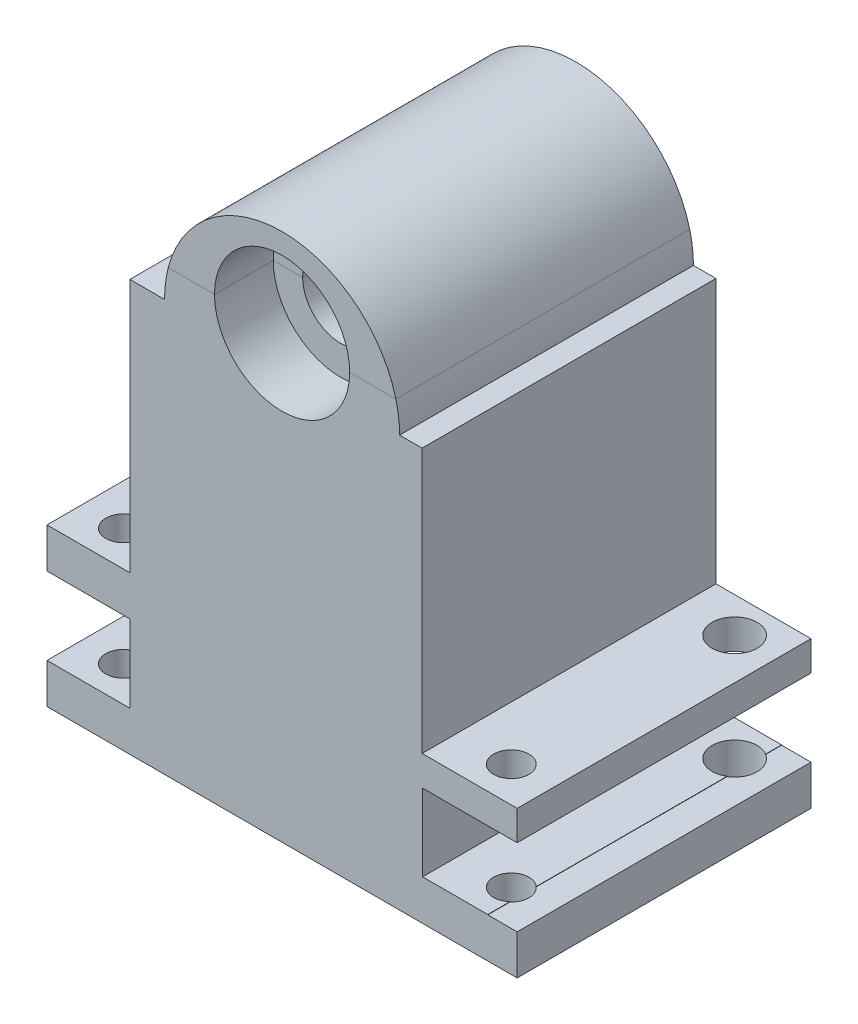
SolidWorks part; units mm, degrees
ref_plane "Plan de face" through (0, 0, 0) normal (0, 0, 1) x (1, 0, 0)
ref_plane "Plan de dessus" through (0, 0, 0) normal (0, 1, 0) x (1, 0, 0)
ref_plane "Plan de droite" through (0, 0, 0) normal (1, 0, 0) x (0, 0, -1)
sketch "Esquisse1" plane through (0, 0, 0) normal (0, 0, 1) x (1, 0, 0)
  line L0 (0, 0) -> (700, 0)
  line L1 (700, 0) -> (700, 450)
  line L2 (700, 450) -> (550, 450)
  line L3 (0, 0) -> (0, 450)
  line L4 (0, 450) -> (150, 450)
  arc A0 (550, 450) -> (150, 450) centre (350, 450) ccw
  dimension "D3" = 200
  dimension "D1" = 700
  dimension "D2" = 450
  dimension "D4" = 150
extrude "Boss.-Extru.1" add sketch "Esquisse1" along normal blind 500
sketch "Esquisse2" plane through (0, 0, 0) normal (0, -1, 0) x (1, 0, 0)
  line L0 (700, 500) -> (700, 0)
  line L1 (700, 0) -> (0, 0)
  line L2 (0, 0) -> (0, 500)
  line L3 (0, 500) -> (700, 500) construction
  line L4 (0, 500) -> (0, 0) construction
  line L5 (0, 500) -> (700, 500)
extrude "Boss.-Extru.2" add sketch "Esquisse2" along normal blind 250
sketch "Esquisse3" plane through (0, 0, 0) normal (0, 0, -1) x (-1, 0, 0)
  circle A0 centre (-350, 500) radius 65
extrude "Enlèv. mat.-Extru.1" cut sketch "Esquisse3" against normal blind 500
sketch "Esquisse4" plane through (0, 0, 0) normal (0, 0, -1) x (-1, 0, 0)
  line L0 (0, -50.3189) -> (-91.0727, -50.3189)
  line L1 (0, 450) -> (0, -250) construction
  line L2 (-91.0727, -50.3189) -> (-91.0727, -181.9886)
  line L3 (-91.0727, -181.9886) -> (0, -181.9886)
  line L4 (0, -181.9886) -> (0, -50.3189)
extrude "Enlèv. mat.-Extru.2" cut sketch "Esquisse4" against normal blind 500
sketch "Esquisse5" plane through (0, 0, 0) normal (0, 0, -1) x (-1, 0, 0)
  line L0 (-700, -181.4044) -> (-589.1123, -181.4044)
  line L1 (-700, -250) -> (-700, 450) construction
  line L2 (-589.1123, -181.4044) -> (-589.1123, -50.6587)
  line L3 (-589.1123, -50.6587) -> (-700, -50.6587)
  line L4 (-700, -50.6587) -> (-700, -181.4044)
extrude "Enlèv. mat.-Extru.3" cut sketch "Esquisse5" against normal blind 500
ref_plane "Plan1" through (0, 500, 0) normal (0, -1, 0) x (-1, 0, 0)
sketch "Esquisse6" plane through (0, 0, 500) normal (0, 0, 1) x (1, 0, 0)
  circle A0 centre (350, 500) radius 115
  circle A1 centre (350, 500) radius 65
extrude "Enlèv. mat.-Extru.4" cut sketch "Esquisse6" against normal blind 100
split "Fractionner2" trim tools "Plan1" bodies to split 108 resulting bodies 109 110
sketch "Esquisse7" plane through (0, 0, 0) normal (0, 0, -1) x (-1, 0, 0)
  circle A0 centre (-350, 500) radius 115
  circle A1 centre (-350, 500) radius 65
extrude "Enlèv. mat.-Extru.5" cut sketch "Esquisse7" against normal blind 100
sketch "Esquisse9" plane through (0, 0, 500) normal (0, 0, 1) x (1, 0, 0)
  line L1 (700, 450) -> (750, 450)
  line L2 (700, 450) -> (700, -50.6587)
  line L3 (700, -50.6587) -> (750, -50.6587)
  line L4 (750, 450) -> (750, -50.6587)
  line L5 (700, -250) -> (750, -250)
  line L6 (700, -250) -> (700, -181.9464)
  line L7 (700, -181.9464) -> (750, -181.9464)
  line L8 (750, -250) -> (750, -181.9464)
  line L9 (0, -50.3189) -> (-50, -50.3189)
  line L10 (0, -50.3189) -> (0, 450)
  line L11 (0, 450) -> (-50, 450)
  line L12 (-50, -50.3189) -> (-50, 450)
  line L13 (0, -181.9886) -> (-50, -181.9886)
  line L14 (0, -181.9886) -> (0, -250)
  line L15 (0, -250) -> (-50, -250)
  line L16 (-50, -181.9886) -> (-50, -250)
  dimension "D1" = 50
  dimension "D2" = 50
extrude "Boss.-Extru.3" add sketch "Esquisse9" against normal blind 500
sketch "Esquisse10" plane through (0, 0, 500) normal (0, 0, 1) x (1, 0, 0)
  line L0 (91.0727, -50.3189) -> (91.0727, 450)
  line L1 (150, 450) -> (-50, 450) construction
  line L2 (91.0727, 450) -> (-50, 450)
  line L3 (-50, 450) -> (-50, 17.6911)
  line L4 (-50, 450) -> (-50, -50.3189) construction
  line L5 (-50, 17.6911) -> (91.0727, 17.6911)
  line L8 (750, 0) -> (588.2822, 0)
  line L9 (750, -50.6587) -> (750, 450) construction
  line L10 (588.2822, 0) -> (588.2822, 450)
  line L11 (750, 450) -> (550, 450) construction
  line L12 (588.2822, 450) -> (750, 450)
  line L13 (750, 450) -> (750, 0)
  line M3 (150, 450) -> (-50, 450)
  line M4 (-50, 450) -> (-50, -50.3189)
  line M16 (750, -50.6587) -> (750, 450)
  line M17 (750, 450) -> (550, 450)
  dimension "D1" = 68.01
extrude "Enlèv. mat.-Extru.6" cut sketch "Esquisse10" against normal blind 500 contours L10 L8 M16 M17 | L5 L0 M4 M3 region at (20.5364, 233.8456, 500) region at (669.1411, 225, 500)
sketch "Esquisse11" plane through (0, 17.6911, 0) normal (0, 1, 0) x (1, 0, 0)
  line L0 (-50, 0) -> (91.0727, 0) construction
  line L1 (-50, 0) -> (-50, -500) construction
  line L2 (-50, -500) -> (91.0727, -500) construction
  circle A0 centre (20, -60) radius 30
  circle A1 centre (20, -440) radius 30
  dimension "D1" = 60
  dimension "D3" = 70
  dimension "D2" = 70
  dimension "D4" = 60
extrude "Enlèv. mat.-Extru.7" cut sketch "Esquisse11" against normal blind 310
sketch "Esquisse12" plane through (0, 0, 0) normal (0, 1, 0) x (1, 0, 0)
  line L0 (750, 0) -> (588.2822, 0) construction
  line L1 (750, 0) -> (750, -500) construction
  line L2 (750, -500) -> (588.2822, -500) construction
  circle A0 centre (680, -60) radius 38.3342
  circle A1 centre (680, -440) radius 30
  dimension "D3" = 60
  dimension "D1" = 60
  dimension "D2" = 70
extrude "Enlèv. mat.-Extru.8" cut sketch "Esquisse12" against normal blind 310
